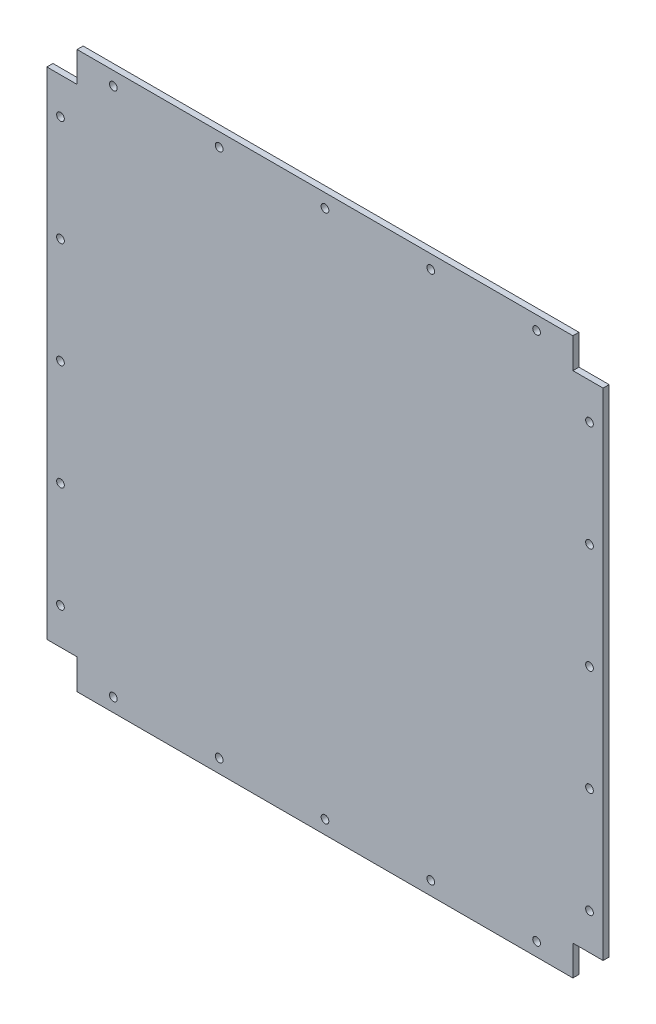
SolidWorks part; units mm, degrees
ref_plane "前视基准面" through (0, 0, 0) normal (0, 0, 1) x (1, 0, 0)
ref_plane "上视基准面" through (0, 0, 0) normal (0, 1, 0) x (1, 0, 0)
ref_plane "右视基准面" through (0, 0, 0) normal (1, 0, 0) x (0, 0, -1)
sketch "草图1" plane through (0, 0, 0) normal (0, 0, 1) x (1, 0, 0)
  line L1 (184, -184) -> (-184, -184)
  line L2 (184, -184) -> (184, 184)
  line L3 (184, 184) -> (-184, 184)
  line L4 (-184, -184) -> (-184, 184)
  line L5 (184, -184) -> (-184, 184) construction
  line L6 (184, 184) -> (-184, -184) construction
  point P0 (0, 0)
  dimension "D1" = 368
  dimension "D2" = 368
extrude "凸台-拉伸1" add sketch "草图1" along normal blind 4
sketch "草图3" plane through (0, 0, 4) normal (0, 0, 1) x (1, 0, 0)
  line L0 (0, -184) -> (0, -175) construction
  line L1 (-184, -184) -> (184, -184) construction
  circle A0 centre (0, -175) radius 2.55
  circle A1 centre (70, -175) radius 2.55
  circle A2 centre (140, -175) radius 2.55
  circle A3 centre (-70, -175) radius 2.55
  circle A4 centre (-140, -175) radius 2.55
  circle A30 centre (-175, 140) radius 2.55
  circle A31 centre (-175, 70) radius 2.55
  circle A32 centre (-175, -70) radius 2.55
  circle A33 centre (-175, -140) radius 2.55
  circle A34 centre (-175, 0) radius 2.55
  circle A35 centre (140, 175) radius 2.55
  circle A36 centre (70, 175) radius 2.55
  circle A37 centre (-70, 175) radius 2.55
  circle A38 centre (-140, 175) radius 2.55
  circle A39 centre (0, 175) radius 2.55
  circle A40 centre (175, -140) radius 2.55
  circle A41 centre (175, -70) radius 2.55
  circle A42 centre (175, 70) radius 2.55
  circle A43 centre (175, 140) radius 2.55
  circle A44 centre (175, 0) radius 2.55
  point P47 (10, -10)
  point P78 (0, 0)
  dimension "D1" = 5.1
  dimension "D2" = 9
  dimension "D3" = 3
  dimension "D4" = 3
  dimension "D6" = 4
extrude "切除-拉伸2" cut sketch "草图3" against normal through all
sketch "草图4" plane through (0, 0, 4) normal (0, 0, 1) x (1, 0, 0)
  line L0 (-164, 184) -> (-164, 164)
  line L1 (-184, -184) -> (-164, -184)
  line L2 (-184, -184) -> (-184, -164)
  line L3 (-184, -164) -> (-164, -164)
  line L4 (-164, -184) -> (-164, -164)
  line L5 (-184, 164) -> (-164, 164)
  line L6 (-184, 184) -> (-164, 184)
  line L7 (-184, 184) -> (-184, 164)
  line L8 (184, 164) -> (164, 164)
  line L9 (164, 184) -> (164, 164)
  line L10 (184, 184) -> (184, 164)
  line L11 (184, 184) -> (164, 184)
  line L12 (164, -184) -> (164, -164)
  line L13 (184, -164) -> (164, -164)
  line L14 (184, -184) -> (164, -184)
  line L15 (184, -184) -> (184, -164)
  point P20 (0, 0)
  dimension "D1" = 20
  dimension "D2" = 20
  dimension "D3" = 4
extrude "切除-拉伸3" cut sketch "草图4" against normal through all contours L0 L5 L7 L6 | L8 L9 L11 L10 | L12 L13 L15 L14 | L2 L1 L4 L3
